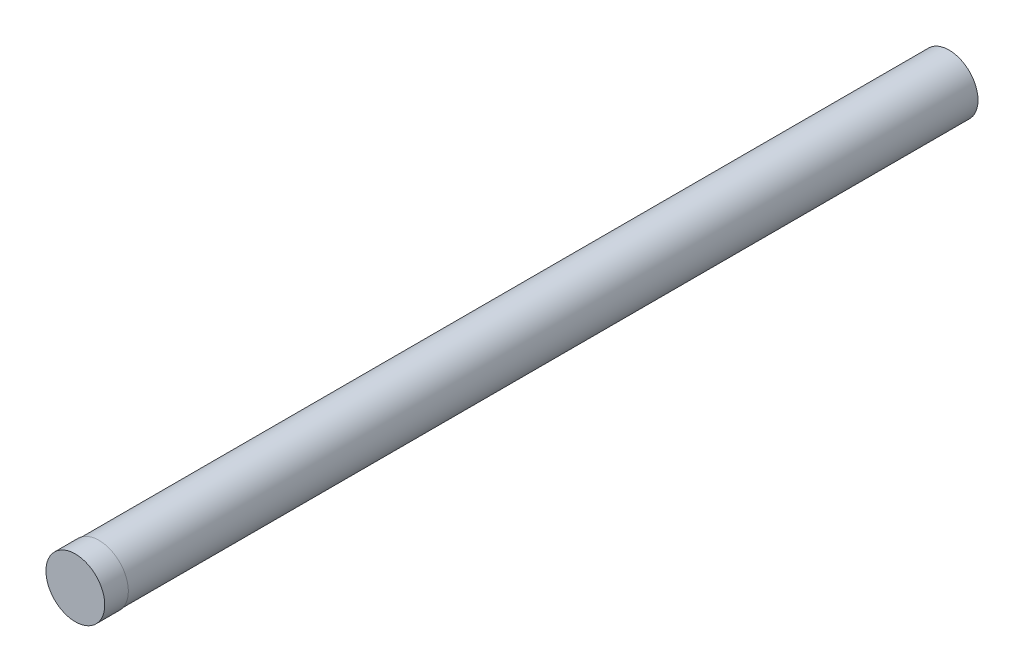
SolidWorks part; units mm, degrees
ref_plane "Front Plane" through (0, 0, 0) normal (0, 0, 1) x (1, 0, 0)
ref_plane "Top Plane" through (0, 0, 0) normal (0, 1, 0) x (1, 0, 0)
ref_plane "Right Plane" through (0, 0, 0) normal (1, 0, 0) x (0, 0, -1)
sketch "Sketch1" plane through (0, 0, 0) normal (0, 0, 1) x (1, 0, 0)
  circle A0 centre (0, 0) radius 2.45
  dimension "D1" = 4.9
extrude "Boss-Extrude1" add sketch "Sketch1" along normal blind 10 and the other way blind 64
sketch "Sketch2" plane through (0, 0, 0) normal (0, 0, 1) x (1, 0, 0)
  circle A0 centre (0, 0) radius 2.5 construction
  dimension "D1" = 5
sketch "Sketch3" plane through (0, 0, 10) normal (0, 0, 1) x (1, 0, 0)
  circle A0 centre (0, 0) radius 2.49
  dimension "D1" = 4.98
extrude "Boss-Extrude2" add sketch "Sketch3" against normal blind 2
